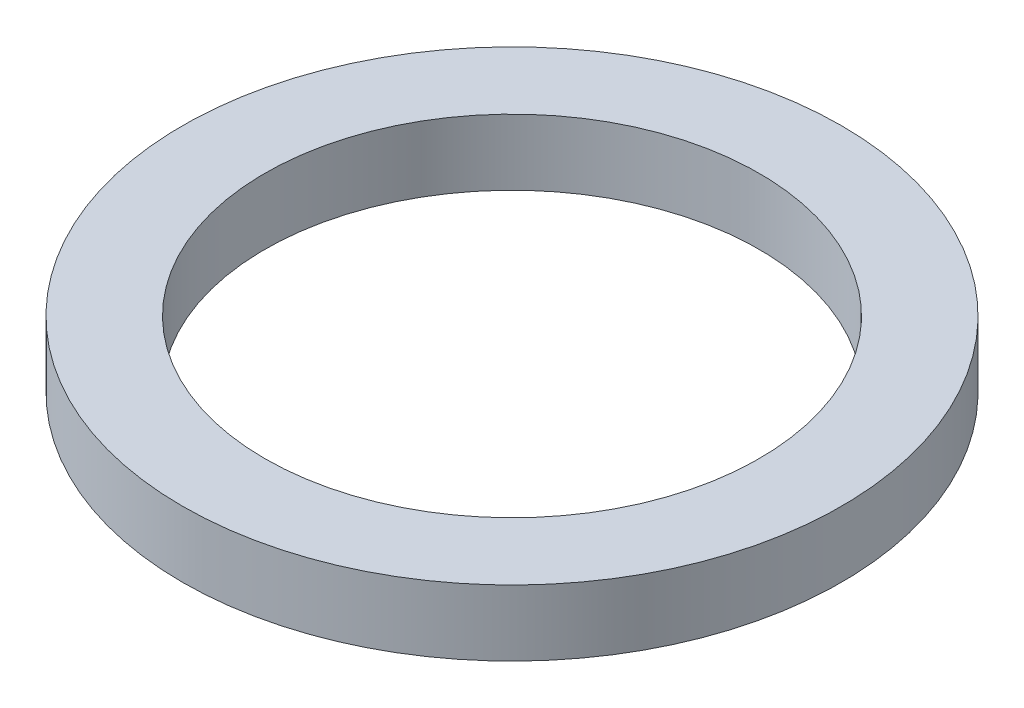
SolidWorks part; units mm, degrees
ref_plane "Front Plane" through (0, 0, 0) normal (0, 0, 1) x (1, 0, 0)
ref_plane "Top Plane" through (0, 0, 0) normal (0, 1, 0) x (1, 0, 0)
ref_plane "Right Plane" through (0, 0, 0) normal (1, 0, 0) x (0, 0, -1)
sketch "Sketch1" plane through (0, 0, 0) normal (0, 1, 0) x (1, 0, 0)
  circle A0 centre (0, 0) radius 50
  dimension "FLANGE_OD" = 100
extrude "Boss-Extrude1" add sketch "Sketch1" along normal blind 10
sketch "Sketch2" plane through (0, 0, 0) normal (0, 1, 0) x (1, 0, 0)
  circle A0 centre (0, 0) radius 37.5
  dimension "BORE_D" = 75
extrude "Cut-Extrude1" cut sketch "Sketch2" along normal through all
sketch "Sketch3" plane through (0, 10, 0) normal (0, 1, 0) x (1, 0, 0)
  circle A0 centre (0, 0) radius 21.4431 construction
  circle A1 centre (-21.4431, 0) radius 1.5992
  dimension "BOLT_D" = 3.1983
  dimension "BOLT_PCD" = 42.8863
extrude "Cut-Extrude2" cut sketch "Sketch3" against normal blind 8.1914 rebuild error yes
pattern_circular "CirPattern1" count 8 over 360 rebuild error yes
